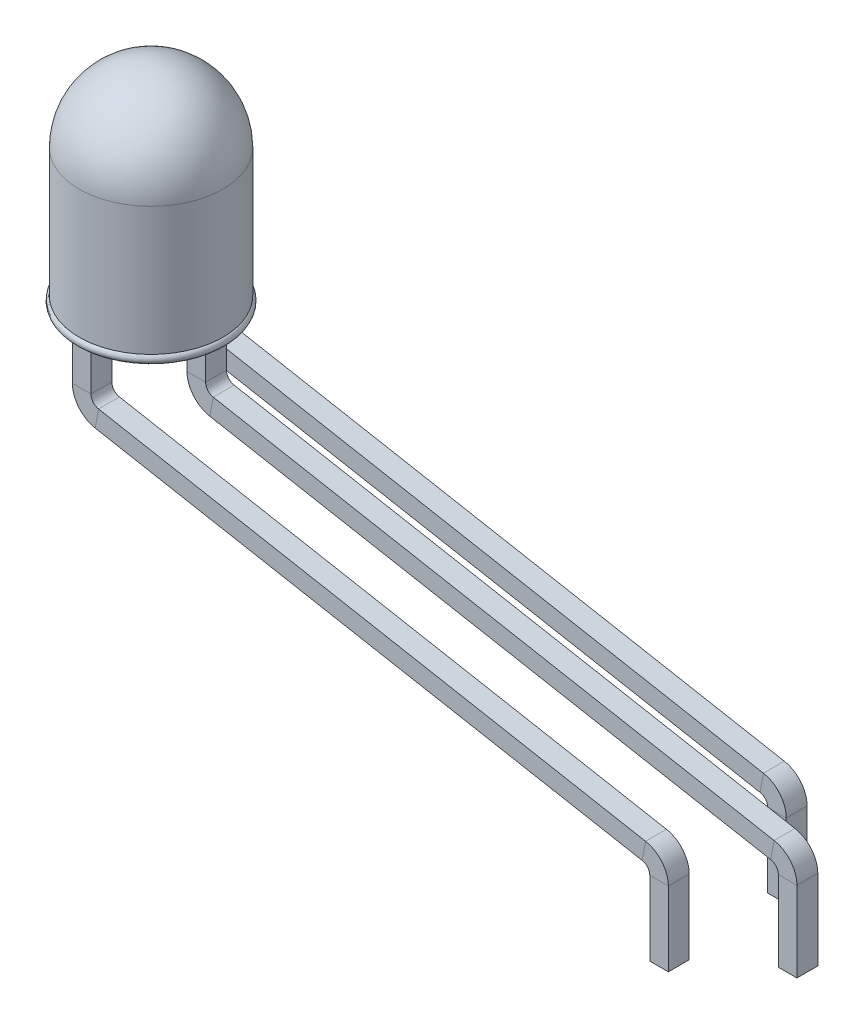
SolidWorks part; units mm, degrees
ref_plane "Front Plane" through (0, 0, 0) normal (0, 0, 1) x (1, 0, 0)
ref_plane "Top Plane" through (0, 0, 0) normal (0, 1, 0) x (1, 0, 0)
ref_plane "Right Plane" through (0, 0, 0) normal (1, 0, 0) x (0, 0, -1)
sketch "Sketch1" plane through (0, 0, 0) normal (0, 0, 1) x (1, 0, 0)
  line L0 (0, 0) -> (-1.5, 0)
  line L1 (-1.55, 0.1866) -> (-1.55, 2.95)
  line L2 (0, 4.5) -> (0, 0) construction
  line L3 (-0.5895, 4.5) -> (0, 4.5) construction
  line L4 (-1.6, 0) -> (-1.6, 1.9354) construction
  line L5 (0, 4.5) -> (0, 0)
  arc A0 (-1.5, 0) -> (-1.55, 0.1866) centre (-1.5, 0.1) cw
  arc A1 (-1.55, 2.95) -> (0, 4.5) centre (0, 2.95) cw
  dimension "D3" = 0.1
  dimension "D1" = 1.6
  dimension "D2" = 0.05
  dimension "D4" = 4.5
revolve "Revolve1" add sketch "Sketch1" angle 360 about L5
sketch "Sketch2" plane through (0, 0, 0) normal (0, -1, 0) x (1, 0, 0)
  line L0 (0, 1.045) -> (0, -1.045) construction
  line L1 (-0.2, 1.495) -> (0.2, 1.495)
  line L2 (-0.2, 1.495) -> (-0.2, 1.045)
  line L3 (-0.2, 1.045) -> (0.2, 1.045)
  line L4 (0.2, 1.495) -> (0.2, 1.045)
  line L5 (-0.2, -1.045) -> (0.2, -1.045)
  line L6 (-0.2, -1.045) -> (-0.2, -1.495)
  line L7 (-0.2, -1.495) -> (0.2, -1.495)
  line L8 (0.2, -1.045) -> (0.2, -1.495)
  point P10 (0, 0)
  point P13 (0.2, -1.27)
  point P15 (0.2, 1.27)
  dimension "D1" = 0.45
  dimension "D2" = 0.4
  dimension "D3" = 2.54
sketch "Sketch4" plane through (0, 0, 0) normal (0, 0, 1) x (1, 0, 0)
  line L0 (0, 0) -> (0, -0.8)
  line L1 (-1.5, 0) -> (1.5, 0) construction
  line L2 (0.3274, -1.1934) -> (12.1126, -3.3679)
  line L3 (12.44, -3.7613) -> (12.44, -5.3613)
  arc A0 (12.1126, -3.3679) -> (12.44, -3.7613) centre (12.04, -3.7613) cw
  arc A1 (0, -0.8) -> (0.3274, -1.1934) centre (0.4, -0.8) ccw
  point P0 (12.44, -5.3613)
  point P17 (12.44, -3.4284)
  point P20 (0, -1.1329)
  dimension "D4" = 0.4
  dimension "D1" = 12.44
  dimension "D2" = 1.6
  dimension "D3" = 12.65
  dimension "D5" = 0.8
sketch "Sketch3" plane through (0, 0, 0) normal (0, -1, 0) x (1, 0, 0)
  line L1 (1, 0.225) -> (1.4, 0.225)
  line L2 (1, 0.225) -> (1, -0.225)
  line L3 (1, -0.225) -> (1.4, -0.225)
  line L4 (1.4, 0.225) -> (1.4, -0.225)
  line L6 (0, 0) -> (1, 0) construction
  line L7 (-0.2, 1.045) -> (0.2, 1.045) construction
  line L8 (0.2, 1.495) -> (0.2, 1.045) construction
  dimension "D1" = 1
sweep "Sweep1" add profiles "Sketch2" path "Sketch4"
sketch "Sketch6" plane through (0, 0, 0) normal (0, -1, 0) x (1, 0, 0)
  line L0 (-0.2, 1.495) -> (-0.2, 1.045) construction
  line L1 (1, 0.225) -> (1.4, 0.225)
  line L2 (1, 0.225) -> (1, -0.225)
  line L3 (1, -0.225) -> (1.4, -0.225)
  line L4 (1.4, 0.225) -> (1.4, -0.225)
  line L5 (-0.2, 1.045) -> (0.2, 1.045) construction
  line L6 (1, 0) -> (0, 0) construction
  dimension "D1" = 1
sketch "Sketch7" plane through (0, 0, 0) normal (0, 0, 1) x (1, 0, 0)
  line L0 (1.2, 0) -> (1.2, -0.6147)
  line L1 (1, 0) -> (1.4, 0) construction
  line L2 (0.3274, -1.1934) -> (12.1126, -3.3679) construction
  line L3 (1.5274, -1.008) -> (13.6126, -3.238)
  line L4 (13.94, -3.6313) -> (13.94, -5.3613)
  arc A0 (1.2, -0.6147) -> (1.5274, -1.008) centre (1.6, -0.6147) ccw
  arc A1 (13.6126, -3.238) -> (13.94, -3.6313) centre (13.54, -3.6313) cw
  arc A2 (0, -0.8) -> (0.3274, -1.1934) centre (0.4, -0.8) ccw construction
  arc A3 (12.44, -3.7613) -> (12.1126, -3.3679) centre (12.04, -3.7613) ccw construction
  point P6 (1.2, -0.6078)
  point P7 (2, -1.0228)
  point P10 (13.4002, -3.6169)
  point P12 (1.5274, -1.4148)
  point P13 (0, 0)
  point P15 (1.9777, -1.1531)
  point P16 (1.8589, -2.2438)
  point P17 (1.2, -0.5724)
  point P25 (13.0417, -3.3175)
  point P26 (13.94, -4.4413)
  point P27 (12.1376, -2.9658)
  point P28 (13.2283, -3.1671)
  dimension "D1" = 1.5
  dimension "D2" = 0.4
sweep "Sweep2" add profiles "Sketch6" path "Sketch7"
